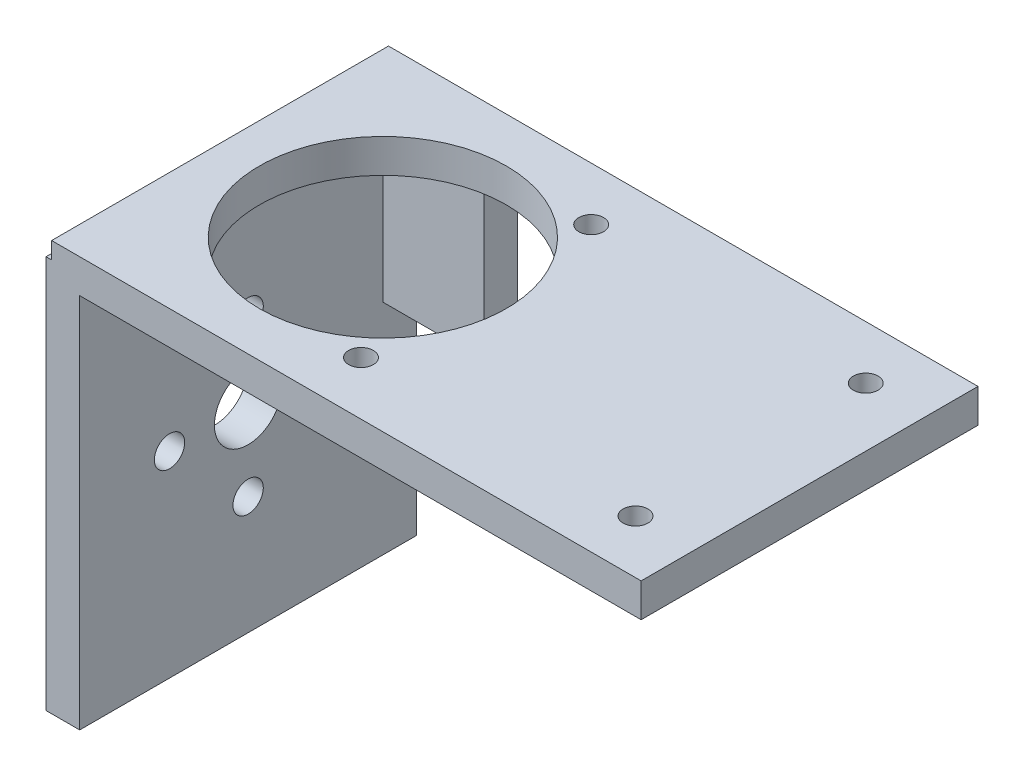
SolidWorks part; units mm, degrees
ref_plane "Front Plane" through (0, 0, 0) normal (0, 0, 1) x (1, 0, 0)
ref_plane "Top Plane" through (0, 0, 0) normal (0, 1, 0) x (1, 0, 0)
ref_plane "Right Plane" through (0, 0, 0) normal (1, 0, 0) x (0, 0, -1)
ref_plane "PZ_m15_000" through (0, 0, -15) normal (0, 0, 1) x (1, 0, 0)
sketch "S_box1" plane through (0, 0, -15) normal (0, 0, 1) x (1, 0, 0)
  line L0 (-15, -17.5) -> (-12, -17.5)
  line L1 (-12, -17.5) -> (-12, 17.5)
  line L2 (-12, 17.5) -> (-15, 17.5)
  line L3 (-15, 17.5) -> (-15, -17.5)
  dimension "P1" = 15
  dimension "P2" = 17.5
  dimension "P3" = 12
  dimension "P4" = 17.5
  dimension "P5" = 12
  dimension "P6" = 17.5
  dimension "P7" = 15
  dimension "P8" = 17.5
extrude "Boss_1" add sketch "S_box1" along normal blind 30
sketch "S_box2" plane through (0, 0, -15) normal (0, 0, 1) x (1, 0, 0)
  line L0 (-14.5, 16) -> (38, 16)
  line L1 (38, 16) -> (38, 19)
  line L2 (38, 19) -> (-14.5, 19)
  line L3 (-14.5, 19) -> (-14.5, 16)
  dimension "P1" = 14.5
  dimension "P2" = 16
  dimension "P3" = 38
  dimension "P4" = 16
  dimension "P5" = 38
  dimension "P6" = 19
  dimension "P7" = 14.5
  dimension "P8" = 19
extrude "Boss_2" add sketch "S_box2" along normal blind 30
sketch "S_box3" plane through (0, 0, -15) normal (0, 0, 1) x (1, 0, 0)
  line L0 (-14.5, 2) -> (-3, 2)
  line L1 (-3, 2) -> (-3, 18.5)
  line L2 (-3, 18.5) -> (-14.5, 18.5)
  line L3 (-14.5, 18.5) -> (-14.5, 2)
  dimension "P1" = 14.5
  dimension "P2" = 2
  dimension "P3" = 3
  dimension "P4" = 2
  dimension "P5" = 3
  dimension "P6" = 18.5
  dimension "P7" = 14.5
  dimension "P8" = 18.5
extrude "Boss_3" add sketch "S_box3" along normal blind 3
ref_plane "PX_m15_100" through (-15.1, 0, 0) normal (1, 0, 0) x (0, 0, -1)
sketch "S_hole4" plane through (-15.1, 0, 0) normal (1, 0, 0) x (0, 0, -1)
  circle A0 centre (0, 0) radius 3
  dimension "D1_S_hole4" = 6
extrude "Hole_4" cut sketch "S_hole4" along normal blind 3.2
sketch "S_hole5" plane through (-15.1, 0, 0) normal (1, 0, 0) x (0, 0, -1)
  circle A0 centre (0, -7) radius 1.35
  dimension "D1_S_hole5" = 2.7
  dimension "P2" = 7
extrude "Hole_5" cut sketch "S_hole5" along normal blind 3.2
sketch "S_hole6" plane through (-15.1, 0, 0) normal (1, 0, 0) x (0, 0, -1)
  circle A0 centre (-7, 0) radius 1.35
  dimension "D1_S_hole6" = 2.7
  dimension "P2" = 7
extrude "Hole_6" cut sketch "S_hole6" along normal blind 3.2
sketch "S_hole7" plane through (-15.1, 0, 0) normal (1, 0, 0) x (0, 0, -1)
  circle A0 centre (0, 7) radius 1.35
  dimension "D1_S_hole7" = 2.7
  dimension "P2" = 7
extrude "Hole_7" cut sketch "S_hole7" along normal blind 3.2
sketch "S_hole8" plane through (-15.1, 0, 0) normal (1, 0, 0) x (0, 0, -1)
  circle A0 centre (7, 0) radius 1.35
  dimension "D1_S_hole8" = 2.7
  dimension "P2" = 7
extrude "Hole_8" cut sketch "S_hole8" along normal blind 3.2
ref_plane "PY_p15_900" through (0, 15.9, 0) normal (0, 1, 0) x (1, 0, 0)
sketch "S_hole9" plane through (0, 15.9, 0) normal (0, 1, 0) x (1, 0, 0)
  circle A0 centre (0, 0) radius 11
  dimension "D1_S_hole9" = 22
extrude "Hole_9" cut sketch "S_hole9" along normal blind 3.2
sketch "S_hole10" plane through (0, 15.9, 0) normal (0, 1, 0) x (1, 0, 0)
  circle A0 centre (8.3, 10.25) radius 1.1
  dimension "D1_S_hole10" = 2.2
  dimension "P2" = 8.3
  dimension "P3" = 10.25
extrude "Hole_10" cut sketch "S_hole10" along normal blind 3.2
sketch "S_hole11" plane through (0, 15.9, 0) normal (0, 1, 0) x (1, 0, 0)
  circle A0 centre (8.3, -10.25) radius 1.1
  dimension "D1_S_hole11" = 2.2
  dimension "P2" = 8.3
  dimension "P3" = 10.25
extrude "Hole_11" cut sketch "S_hole11" along normal blind 3.2
sketch "S_hole12" plane through (0, 15.9, 0) normal (0, 1, 0) x (1, 0, 0)
  circle A0 centre (32.75, 10.25) radius 1.1
  dimension "D1_S_hole12" = 2.2
  dimension "P2" = 32.75
  dimension "P3" = 10.25
extrude "Hole_12" cut sketch "S_hole12" along normal blind 3.2
sketch "S_hole13" plane through (0, 15.9, 0) normal (0, 1, 0) x (1, 0, 0)
  circle A0 centre (32.75, -10.25) radius 1.1
  dimension "D1_S_hole13" = 2.2
  dimension "P2" = 32.75
  dimension "P3" = 10.25
extrude "Hole_13" cut sketch "S_hole13" along normal blind 3.2
equation "\"plate_t\" = 3"
equation "\"clearance\" = 0.4"
